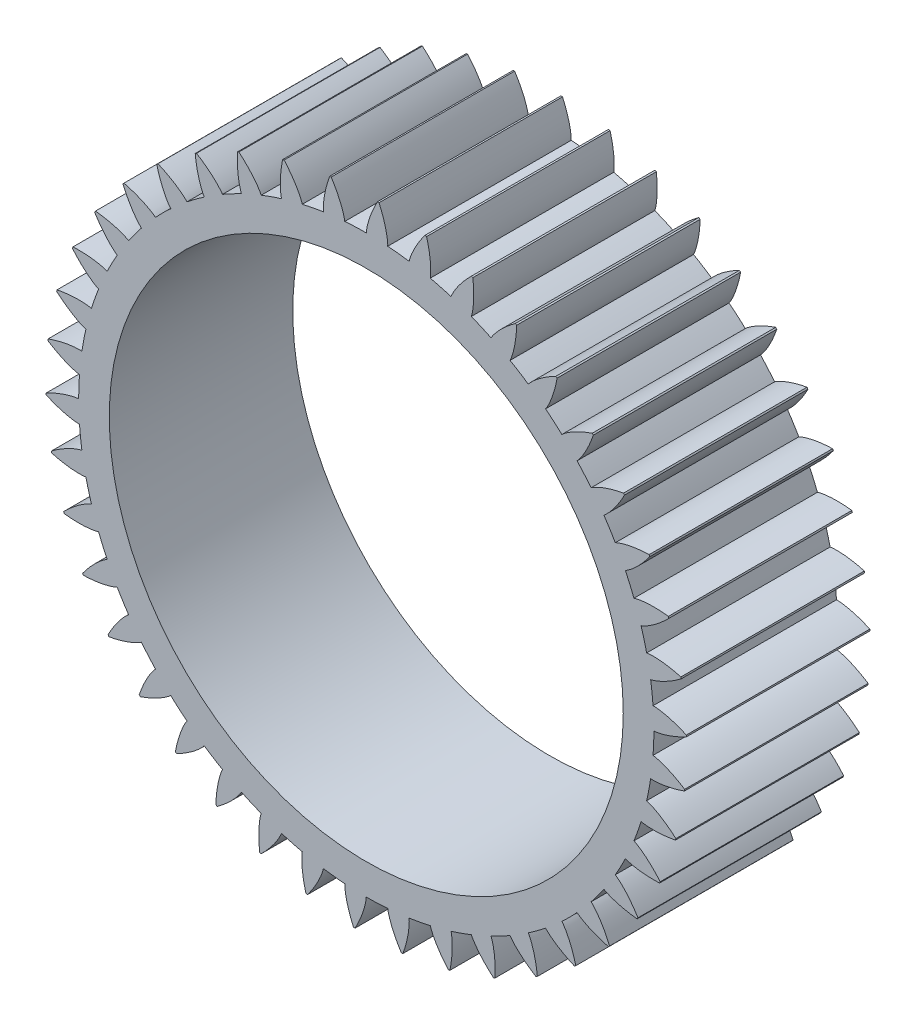
SolidWorks part; units mm, degrees
ref_plane "Front Plane" through (0, 0, 0) normal (0, 0, 1) x (1, 0, 0)
ref_plane "Top Plane" through (0, 0, 0) normal (0, 1, 0) x (1, 0, 0)
ref_plane "Right Plane" through (0, 0, 0) normal (1, 0, 0) x (0, 0, -1)
sketch "Sketch1" plane through (0, 0, 0) normal (0, 0, 1) x (1, 0, 0)
  line L0 (0, 0) -> (52.3443, -1.9586) construction
  line L1 (0, 0) -> (52.3443, 1.9586) construction
  line L2 (0, 0) -> (52.3443, -1.9586) construction
  line L3 (0, 0) -> (52.381, 0) construction
  line L4 (0, 0) -> (52.0516, 5.8648) construction
  line L5 (41.9944, 1.5713) -> (52.3443, 1.9586)
  line L6 (41.9944, -1.5713) -> (46.9909, -1.7583)
  line L7 (46.9846, 0) -> (48.983, 0)
  circle A0 centre (0, 0) radius 50 construction
  circle A1 centre (0, 0) radius 47.0238 construction
  circle A2 centre (0, 0) radius 46.9846 construction
  circle A3 centre (0, 0) radius 52.381 construction
  arc A4 (41.9944, 1.5713) -> (41.9944, -1.5713) centre (0, 0) cw
  arc A5 (46.9847, -1.9184) -> (46.9909, -1.7583) centre (0, 0) cw
  arc A6 (52.3443, 1.9586) -> (52.349, 1.8297) centre (0, 0) cw
  spline S0 degree 4 poles (46.9846, 0) (47.0467, 0.0018) (47.1706, 0.0089) (47.4054, 0.0347) (47.7494, 0.0889) (48.3388, 0.21) (49.2603, 0.4646) (50.4706, 0.9041) (52.1042, 1.6596) (53.9325, 2.7102) (55.836, 4.0308) (57.7649, 5.6167) (59.5726, 7.3388) (61.2614, 9.1774) (62.9111, 11.2123) (64.7951, 13.8529) (66.7982, 17.1643) (68.785, 21.1974) (70.5742, 25.8619) (71.9606, 30.6607) (72.96, 35.5541) (73.5094, 39.8891) (73.7576, 43.6247) (73.8205, 46.743) (73.7863, 49.2381) (73.6695, 51.7304) (73.4717, 54.2178) (73.1257, 57.3172) (72.6504, 60.4009) (72.1108, 63.1551) (71.5463, 65.5867) (71.2166, 66.8909) (71.004, 67.6932) (70.8205, 68.3656) (70.621, 69.0756) (70.4517, 69.6602) (70.1201, 70.7707) (69.855, 71.6065) (69.5211, 72.6398) (69.212, 73.5456) (68.8694, 74.527) (68.5321, 75.4491) (68.2609, 76.1741) (68.0833, 76.6328) (67.9907, 76.8718) knots 0 0 0 0 0 0.002802 0.005604 0.010661 0.015718 0.02996 0.048734 0.068727 0.096889 0.125051 0.153212 0.181374 0.209535 0.237696 0.271429 0.327752 0.384075 0.440398 0.496721 0.553044 0.609367 0.637529 0.66569 0.693852 0.722013 0.750174 0.778336 0.834659 0.86282 0.876901 0.890982 0.895509 0.900036 0.909091 0.920455 0.931818 0.943182 0.954545 0.965909 0.977273 0.988636 1 1 1 1 1 construction
  spline S1 degree 4 poles (46.9846, 0) (47.0467, 0.0018) (47.1706, 0.0089) (47.4054, 0.0347) (47.7494, 0.0889) (48.3388, 0.21) (49.2603, 0.4646) (50.4706, 0.9041) (52.1042, 1.6596) (53.9325, 2.7102) (55.836, 4.0308) (57.7649, 5.6167) (59.5726, 7.3388) (61.2614, 9.1774) (62.9111, 11.2123) (64.7951, 13.8529) (66.7982, 17.1643) (68.785, 21.1974) (70.5742, 25.8619) (71.9606, 30.6607) (72.96, 35.5541) (73.5094, 39.8891) (73.7576, 43.6247) (73.8205, 46.743) (73.7863, 49.2381) (73.6695, 51.7304) (73.4717, 54.2178) (73.1257, 57.3172) (72.6504, 60.4009) (72.1108, 63.1551) (71.5463, 65.5867) (71.2166, 66.8909) (71.004, 67.6932) (70.8205, 68.3656) (70.6979, 68.8018) (70.6215, 69.0699) (70.571, 69.2451) knots 0 0 0 0 0 0.002802 0.005604 0.010661 0.015718 0.02996 0.048734 0.068727 0.096889 0.125051 0.153212 0.181374 0.209535 0.237696 0.271429 0.327752 0.384075 0.440398 0.496721 0.553044 0.609367 0.637529 0.66569 0.693852 0.722013 0.750174 0.778336 0.834659 0.86282 0.876901 0.890982 0.895509 0.900036 0.909091 0.909091 0.909091 0.909091 0.909091
  point P10 (46.9909, 1.7583)
  point P21 (47.0238, 0)
  dimension "pitchRadius" = 50
  dimension "addendumRadius" = 52.381
  dimension "dedendumRadius" = 47.0238
  dimension "baseRadius" = 46.9846
  dimension "D1" = 4.286
  dimension "D2" = 2.143
  dimension "toothArc" = 8.571
  dimension "D3" = 5
extrude "Boss-Extrude1" add sketch "Sketch1" along normal blind 30 contours S1 A6 L5 | L7 S1 A5 L5 A4 L6 region at (44.5602, 0, 0) region at (49.0288, 1.1619, 0)
mirror "Mirror1" about plane through (0, 0, 30) normal (-0.0374, 0.9993, 0) of "Boss-Extrude1"
pattern_circular "CirPattern1" count 42 over 360 about axis through (0, 0, 30) along (0, 0, -1) of "Boss-Extrude1", "Mirror1"
ref_axis "Axis1" through (0, 0, 0) along (0, 0, 1)
equation "\"D1@Sketch1\"=\"toothArc@Sketch1\"/2"
equation "\"D2@Sketch1\"=\"toothArc@Sketch1\"/4"
equation "\"pitchRadius\"= 5"
equation "\"nTeeth\"= 42"
equation "\"pressureAngle\"= 20"
equation "\"baseRadius\"= \"pitchRadius\" * cos ( \"pressureAngle\" )"
equation "\"diametralPitch\"= \"nTeeth\" / ( 2 * \"pitchRadius\" )'note units: cm^-1"
equation "\"dedendum\"= 1.25 / \"diametralPitch\"'for full depth, 20 deg pressure angle"
equation "\"addendum\"= 1 / \"diametralPitch\""
equation "\"pitchRadius@Sketch1\"= \"pitchRadius\""
equation "\"addendumRadius@Sketch1\"= \"pitchRadius\" + \"addendum\""
equation "\"dedendumRadius@Sketch1\"= \"pitchRadius\" - \"dedendum\""
equation "\"baseRadius@Sketch1\"= \"baseRadius\""
equation "\"toothArc@Sketch1\"=360/\"nTeeth\""
equation "\"D1@CirPattern1\"=\"nTeeth\""
